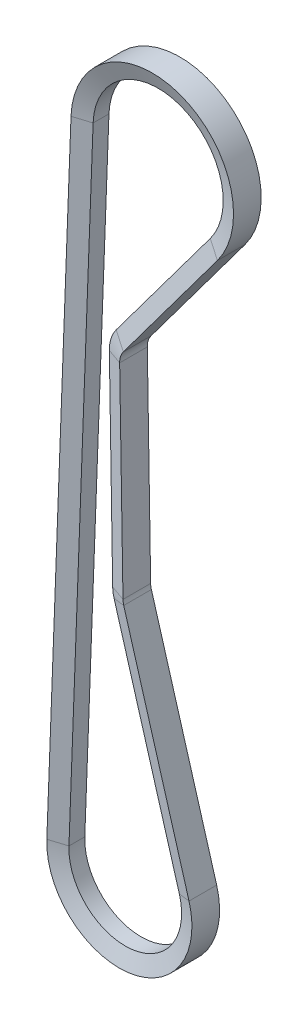
SolidWorks part; units mm, degrees
ref_plane "Front Plane" through (0, 0, 0) normal (0, 0, 1) x (1, 0, 0)
ref_plane "Top Plane" through (0, 0, 0) normal (0, 1, 0) x (1, 0, 0)
ref_plane "Right Plane" through (0, 0, 0) normal (1, 0, 0) x (0, 0, -1)
sketch "Sketch2" plane through (0, 0, 0) normal (0, 0, 1) x (1, 0, 0)
  line L0 (0, 0) -> (1, 0) construction
  line L1 (0, 0) -> (0, 1) construction
  line L12 (-24.9821, 0.9464) -> (-16.6545, 220.7683)
  line L14 (33.7721, 202.9708) -> (1.3646, 159.509)
  line L15 (0.106, 155.6093) -> (1.2504, 85.6187)
  line L16 (1.5047, 83.9406) -> (23.9954, 7.0156)
  arc A4 (-16.6545, 220.7683) -> (33.7721, 202.9708) centre (11.3254, 219.7083) cw
  arc A7 (23.9954, 7.0156) -> (-24.9821, 0.9464) centre (0, 0) cw
  arc A8 (1.3646, 159.509) -> (0.106, 155.6093) centre (6.4552, 155.7132) ccw
  arc A9 (1.2504, 85.6187) -> (1.5047, 83.9406) centre (7.5996, 85.7225) ccw
ref_plane "Plane4" through (23.9954, 7.0156, 0) normal (0.2806, -0.9598, 0) x (-0.9598, -0.2806, 0)
sketch "Sketch3" plane through (23.9954, 7.0156, 0) normal (0.2806, -0.9598, 0) x (-0.9598, -0.2806, 0)
  line L0 (0, -4.7625) -> (0, 4.7625)
  line L1 (0, -4.7625) -> (5.588, -2.7286)
  line L2 (5.588, -2.7286) -> (5.588, 2.7286)
  line L3 (5.588, 2.7286) -> (0, 4.7625)
  line L4 (0, 0) -> (5.588, 0) construction
  dimension "D1" = 9.525
  dimension "D2" = 5.588
  dimension "D3" = 40
sweep "Sweep1" add profiles "Sketch3" path "Sketch2"
